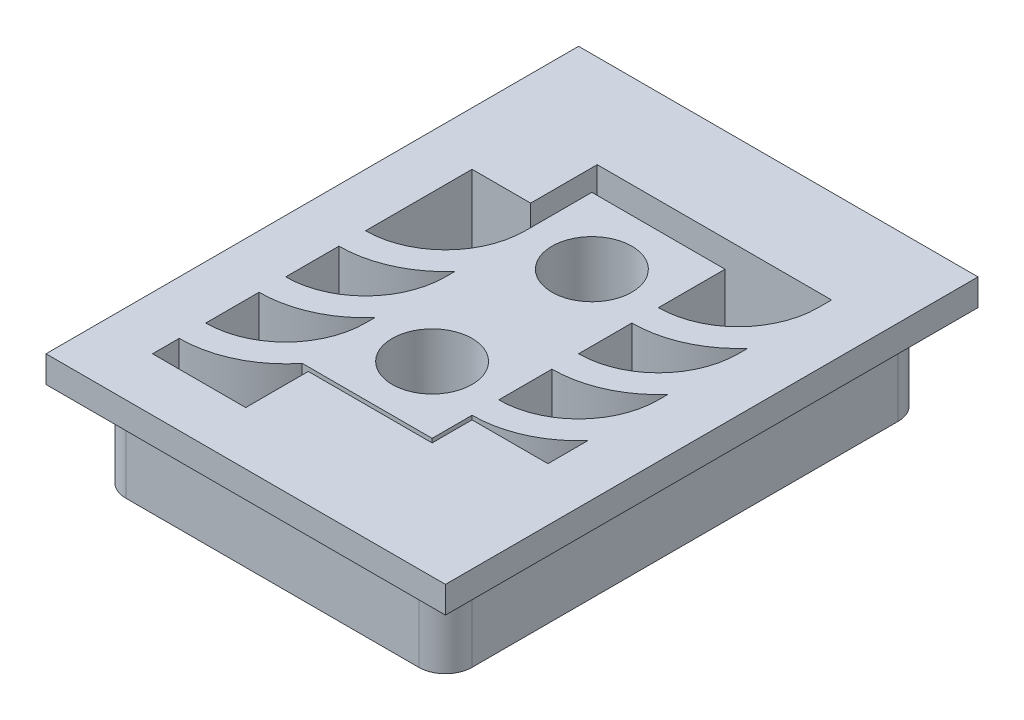
SolidWorks part; units mm, degrees
ref_plane "Front Plane" through (0, 0, 0) normal (0, 0, 1) x (1, 0, 0)
ref_plane "Top Plane" through (0, 0, 0) normal (0, 1, 0) x (1, 0, 0)
ref_plane "Right Plane" through (0, 0, 0) normal (1, 0, 0) x (0, 0, -1)
sketch "Sketch1" plane through (0, 0, 0) normal (0, 1, 0) x (1, 0, 0)
  line L0 (0, -3) -> (0, 3)
  line L2 (6.5, -9) -> (-6.5, -9)
  line L3 (6.5, -9) -> (6.5, 9)
  line L4 (6.5, 9) -> (-6.5, 9)
  line L5 (-6.5, -9) -> (-6.5, 9)
  line L6 (6.5, -9) -> (-6.5, 9) construction
  line L7 (6.5, 9) -> (-6.5, -9) construction
  circle A0 centre (0, 3) radius 1.5
  circle A1 centre (0, -3) radius 1.5
  point P4 (0, 0)
  point P7 (0, 0)
  dimension "D2" = 3
  dimension "D3" = 3
  dimension "D1" = 6
  dimension "D4" = 18
  dimension "D5" = 13
extrude "Boss-Extrude1" add sketch "Sketch1" along normal blind 3.2
sketch "Sketch3" plane through (0, 0, 0) normal (0, -1, 0) x (1, 0, 0)
  line L4 (0, -3) -> (0, 3)
  line L8 (-7.5, 10) -> (-7.5, -10)
  line L9 (-7.5, -10) -> (7.5, -10)
  line L10 (7.5, -10) -> (7.5, 10)
  line L11 (7.5, 10) -> (-7.5, 10)
  line L12 (-7.5, 10) -> (-7.5, -10)
  line L13 (-7.5, -10) -> (7.5, -10)
  line L14 (7.5, -10) -> (7.5, 10)
  line L15 (7.5, 10) -> (-7.5, 10)
  circle A0 centre (0, 3) radius 1.5
  circle A1 centre (0, -3) radius 1.5
  point P5 (0, 0)
  dimension "D3" = 3
  dimension "D4" = 3
  dimension "D2" = 6
  dimension "D1" = 1
extrude "Boss-Extrude2" add sketch "Sketch3" along normal blind 1
fillet "Fillet1" radius 1 4 edges at (6.5, 1.6, 9) (-6.5, 1.6, 9) (-6.5, 1.6, -9) (6.5, 1.6, -9)
sketch "Sketch2" plane through (0, 3.2, 0) normal (0, 1, 0) x (1, 0, 0)
  line L0 (-2.5, -2.6458) -> (-2.5, -3)
  line L1 (0, -5.5) -> (2.5, -5.5)
  line L2 (2.5, -5.5) -> (2.5, -4)
  line L3 (5.5, 6.5) -> (-5.5, 6.5)
  line L4 (-3.3, 8) -> (-3.3, 4)
  line L5 (-2.5, 0.3542) -> (-2.5, 0)
  line L6 (2.5, 3) -> (2.5, -3)
  line L7 (-3.3, 4) -> (-5.5, 4)
  line L8 (0, 5.5) -> (-2.5, 5.5)
  line L9 (-5.5, -8) -> (5.5, -8)
  line L10 (5.5, -8) -> (5.5, 8)
  line L11 (5.5, 8) -> (-5.5, 8)
  line L12 (-5.5, 8) -> (-5.5, -8)
  line L13 (-5.5, -8) -> (5.5, -8)
  line L14 (5.5, -8) -> (5.5, 8)
  line L15 (5.5, 8) -> (-5.5, 8)
  line L16 (-5.5, 8) -> (-5.5, -8)
  line L17 (-2.5, 5.5) -> (-2.5, 3)
  line L18 (0, -5.65) -> (2.65, -5.65)
  line L19 (2.65, -5.65) -> (2.65, -4.15)
  line L20 (0, -5.65) -> (-2, -5.65)
  line L21 (-2, -5.65) -> (-2, -8)
  line L22 (2.65, -4.15) -> (5.5, -4.15)
  line L23 (2.65, -5.65) -> (2.65, -4) construction
  line L24 (0, -5.5) -> (-2.5, -5.5)
  line L25 (-2.5, -5.5) -> (-2.5, -5.6458)
  line L26 (0, 5.5) -> (2.5, 5.5)
  line L27 (2.5, 5.5) -> (2.5, 3)
  arc A0 (-2.5, 3) -> (-5.5, 0) centre (-5.5, 3) cw
  arc A1 (-2.5, -3) -> (-5.5, -6) centre (-5.5, -3) cw
  arc A2 (-2.5, 0) -> (-5.5, -3) centre (-5.5, 0) cw
  arc A3 (-2.5, 0.3542) -> (-5.5, -1) centre (-5.5, 3) cw
  arc A4 (-2.5, -2.6458) -> (-5.5, -4) centre (-5.5, 0) cw
  arc A5 (-1.8636, -4.6664) -> (-5.5, -7) centre (-5.5, -3) cw
  arc A6 (-1.5, 3) -> (-5.5, -1) centre (-5.5, 3) cw construction
  arc A7 (-1.5, 0) -> (-5.5, -4) centre (-5.5, 0) cw construction
  arc A8 (-1.5, -3) -> (-5.5, -7) centre (-5.5, -3) cw construction
  circle A9 centre (0, -3) radius 2.5
  arc A10 (-1.8636, -4.6664) -> (-2.5, -3) centre (0, -3) ccw
  arc A11 (2.5, 3) -> (5.5, 6) centre (2.5, 6) ccw
  circle A12 centre (0, 3) radius 2.5
  circle A13 centre (0, 3) radius 2.5
  arc A14 (2.5, 0) -> (5.5, 3) centre (2.5, 3) ccw
  arc A15 (2.5, -3) -> (5.5, 0) centre (2.5, 0) ccw
  arc A16 (2.5, 2) -> (5.5, 3.3542) centre (2.5, 6) ccw
  arc A17 (2.5, -1) -> (5.5, 0.3542) centre (2.5, 3) ccw
  arc A18 (2.2936, -3.9947) -> (5.5, -2.6458) centre (2.5, 0) ccw
  arc A19 (2.5, -4) -> (6.5, 0) centre (2.5, 0) ccw construction
  arc A20 (2.5, 2) -> (6.5, 6) centre (2.5, 6) ccw construction
  arc A21 (2.5, -1) -> (6.5, 3) centre (2.5, 3) ccw construction
  dimension "D4" = 4
  dimension "D5" = 4
  dimension "D6" = 0.15
  dimension "D7" = 1.5
  dimension "D8" = 2
  dimension "D9" = 1.5
  dimension "D10" = 2.2
  dimension "D11" = 4
  dimension "D1" = 1
  dimension "D2" = 1
  dimension "D3" = 1
extrude "Cut-Extrude1" cut sketch "Sketch2" against normal through all
mirror "Mirror1" about plane through (0, -1, 0) normal (0, -1, 0) of bodies 102
delete or keep bodies "Body-Delete/Keep 1" type keep bodies bodies 107
